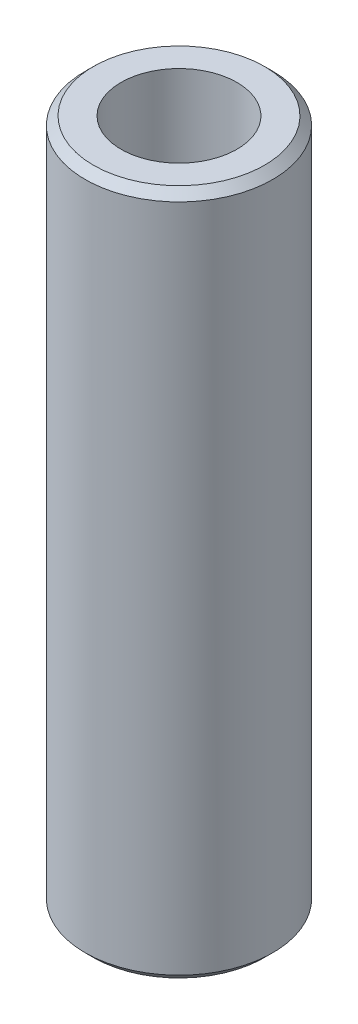
SolidWorks part; units mm, degrees
ref_plane "Front Plane" through (0, 0, 0) normal (0, 0, 1) x (1, 0, 0)
ref_plane "Top Plane" through (0, 0, 0) normal (0, 1, 0) x (1, 0, 0)
ref_plane "Right Plane" through (0, 0, 0) normal (1, 0, 0) x (0, 0, -1)
sketch "Sketch1" plane through (0, 0, 0) normal (0, 1, 0) x (1, 0, 0)
  circle A0 centre (0, 0) radius 47.5
  dimension "SHAFT_OD" = 95
extrude "Boss-Extrude1" add sketch "Sketch1" along normal blind 347.4313
sketch "Sketch2" plane through (0, 0, 0) normal (0, 1, 0) x (1, 0, 0)
  circle A0 centre (0, 0) radius 29.3538
  dimension "BORE_D" = 58.7075
extrude "Cut-Extrude1" cut sketch "Sketch2" along normal through all
chamfer "Chamfer1" distance 4.1711 angle 45 2 edges at (0, 347.4313, 47.5) (0, 0, 47.5)
